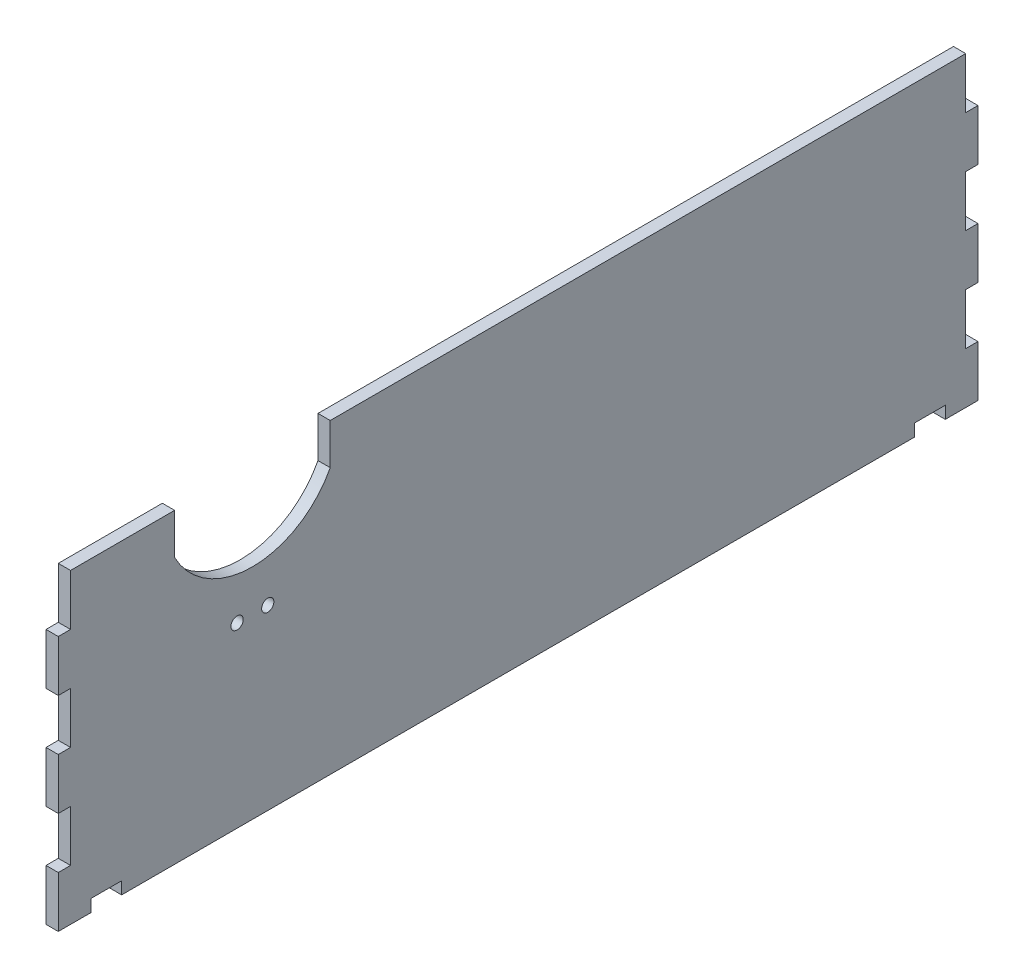
SolidWorks part; units mm, degrees
ref_plane "Front" through (0, 0, 0) normal (0, 0, 1) x (1, 0, 0)
ref_plane "Top" through (0, 0, 0) normal (0, 1, 0) x (1, 0, 0)
ref_plane "Right" through (0, 0, 0) normal (1, 0, 0) x (0, 0, -1)
sketch "Sketch1" plane through (0, 0, 0) normal (1, 0, 0) x (0, 0, -1)
  line L1 (0, 0) -> (-450, 0)
  line L2 (0, 0) -> (0, 150)
  line L3 (0, 150) -> (-450, 150)
  line L4 (-450, 0) -> (-450, 150)
  dimension "D1" = 450
  dimension "D2" = 150
extrude "Boss-Extrude1" add sketch "Sketch1" along normal blind 6
sketch "Sketch2" plane through (6, 0, 0) normal (1, 0, 0) x (0, 0, -1)
  line L0 (-450, 150) -> (-450, 0) construction
  line L1 (-450, 150) -> (-444, 150)
  line L2 (-450, 150) -> (-450, 125)
  line L3 (-450, 125) -> (-444, 125)
  line L4 (-444, 150) -> (-444, 125)
  line L5 (0, 150) -> (-450, 150) construction
  dimension "D1" = 6
  dimension "D2" = 25
extrude "Cut-Extrude1" cut sketch "Sketch2" against normal through all
pattern_linear "LPattern1" count 3 spacing 50 along (0, -1, 0) count 2 spacing 444 along (0, 0, -1) of "Cut-Extrude1"
sketch "Sketch3" plane through (6, 0, 0) normal (1, 0, 0) x (0, 0, -1)
  line L0 (-450, 0) -> (0, 0) construction
  line L1 (-434, 0) -> (-419, 0)
  line L2 (-434, 0) -> (-434, 6)
  line L3 (-434, 6) -> (-419, 6)
  line L4 (-419, 0) -> (-419, 6)
  line L6 (-444, 25) -> (-444, 50) construction
  dimension "D1" = 10
  dimension "D2" = 15
  dimension "D3" = 6
extrude "Cut-Extrude2" cut sketch "Sketch3" against normal through all
pattern_linear "LPattern2" count 2 spacing 403 along (0, 0, -1) of "Cut-Extrude2"
sketch "Sketch4" plane through (6, 0, 0) normal (1, 0, 0) x (0, 0, -1)
  line L0 (-393.0657, 130) -> (-316.9343, 130) construction
  line L1 (-355, 150) -> (-355, 107) construction
  line L2 (-450, 125) -> (-450, 100) construction
  line L3 (-393.0657, 130) -> (-393.0657, 150)
  line L4 (-6, 150) -> (-444, 150) construction
  line L5 (-393.0657, 150) -> (-316.9343, 150)
  line L6 (-316.9343, 150) -> (-316.9343, 130)
  arc A0 (-393.0657, 130) -> (-316.9343, 130) centre (-355, 150) ccw
  circle A1 centre (-362.5, 87) radius 3
  circle A3 centre (-347.5, 87) radius 3
  dimension "D4" = 63
  dimension "D1" = 43
  dimension "D6" = 6
  dimension "D2" = 20
  dimension "D3" = 95
  dimension "D5" = 7.5
extrude "Cut-Extrude3" cut sketch "Sketch4" against normal blind 10
